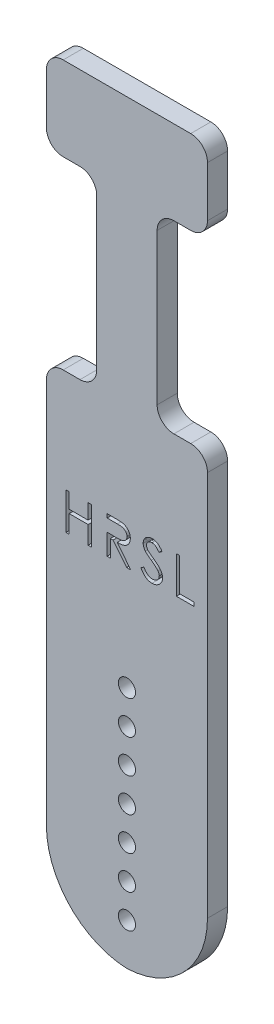
SolidWorks part; units mm, degrees
other "Markup1"
sketch "Sketch7" plane through (-20, 225, -2) normal (-0.1146, 0.1086, -0.9875) x (-0.991, 0.0573, 0.1213)
sketch "Sketch10" plane through (-20, 225, -2) normal (-0.1146, 0.1086, -0.9875) x (-0.991, 0.0573, 0.1213)
sketch "Sketch11" plane through (-20, 225, -2) normal (-0.1146, 0.1086, -0.9875) x (-0.991, 0.0573, 0.1213)
sketch "Sketch13" plane through (-25, 225, -3) normal (-0.1146, 0.1086, -0.9875) x (-0.991, 0.0573, 0.1213)
sketch "Sketch14" plane through (-24, 225, -3) normal (-0.1146, 0.1086, -0.9875) x (-0.991, 0.0573, 0.1213)
sketch "Sketch15" plane through (-24, 225, -3) normal (-0.1146, 0.1086, -0.9875) x (-0.991, 0.0573, 0.1213)
ref_plane "Front Plane" through (0, 0, 0) normal (0, 0, 1) x (1, 0, 0)
ref_plane "Top Plane" through (0, 0, 0) normal (0, 1, 0) x (1, 0, 0)
ref_plane "Right Plane" through (0, 0, 0) normal (1, 0, 0) x (0, 0, -1)
sketch "Sketch1" plane through (0, 0, 0) normal (0, 1, 0) x (1, 0, 0)
  line L1 (-24, 3) -> (24, 3)
  line L2 (-24, 3) -> (-24, -3)
  line L3 (-24, -3) -> (24, -3)
  line L4 (24, 3) -> (24, -3)
  line L5 (-24, 3) -> (24, -3) construction
  line L6 (-24, -3) -> (24, 3) construction
  point P0 (0, 0)
  dimension "D1" = 6
  dimension "D2" = 48
extrude "Boss-Extrude1" add sketch "Sketch1" along normal blind 225
fillet "Fillet1" radius 25 2 edges at (-24, 0, 0) (24, 0, 0)
sketch "Sketch2" plane through (0, 0, 3) normal (0, 0, 1) x (1, 0, 0)
  circle A0 centre (0, 12.5) radius 2.55
extrude "Cut-Extrude1" cut sketch "Sketch2" against normal through all
pattern_linear "LPattern1" count 7 spacing 10 along (0, 1, 0) of "Cut-Extrude1"
sketch "Sketch12" plane through (0, 0, 0) normal (0, 0, 1) x (1, 0, 0)
  line L3 (-24, 200) -> (24, 200)
  line L5 (0, 232.0388) -> (0, 196.5997) construction
  line L6 (-9, 200) -> (-9, 145)
  line L7 (9, 200) -> (9, 145)
  line L8 (9, 145) -> (24, 145)
  line L9 (24, 225) -> (24, 25) construction
  line L10 (24, 145) -> (24, 200)
  line L12 (-9, 145) -> (-24, 145)
  line L13 (-24, 225) -> (-24, 25) construction
  line L14 (-24, 145) -> (-24, 200)
  line L15 (24, 225) -> (-24, 225) construction
  dimension "D1" = 15
  dimension "D2" = 55
  dimension "D3" = 18
  dimension "D4" = 9
  dimension "D5" = 55
  dimension "D6" = 48
  dimension "D7" = 55
  dimension "D8" = 15
  dimension "D9" = 25
extrude "Cut-Extrude2" cut sketch "Sketch12" against normal through all both and the other way through all contours L12 L6 L3 | L3 L7 L8 region at (16.5, 172.5, 0) region at (-16.5, 172.5, 0)
fillet "Fillet2" radius 5 10 edges at (-24, 145, 0) (-9, 145, 0) (24, 145, 0) (9, 145, 0) (9, 200, 0) (-9, 200, 0) (-24, 225, 0) (-24, 200, 0) (24, 200, 0) (24, 225, 0)
sketch "Sketch19" plane through (0, 0, -3) normal (0, 0, -1) x (-1, 0, 0)
  line L0 (18.2062, 114.4599) -> (17.2191, 114.4599)
  line L1 (17.2191, 114.4599) -> (17.2191, 109.9471)
  line L2 (17.2191, 109.9471) -> (11.578, 109.9471)
  line L3 (11.578, 109.9471) -> (11.578, 114.4599)
  line L4 (11.578, 114.4599) -> (10.5909, 114.4599)
  line L5 (10.5909, 114.4599) -> (10.5909, 103.4599)
  line L6 (10.5909, 103.4599) -> (11.578, 103.4599)
  line L7 (11.578, 103.4599) -> (11.578, 108.8189)
  line L8 (11.578, 108.8189) -> (17.2191, 108.8189)
  line L9 (17.2191, 108.8189) -> (17.2191, 103.4599)
  line L10 (17.2191, 103.4599) -> (18.2062, 103.4599)
  line L11 (18.2062, 103.4599) -> (18.2062, 114.4599)
  line L12 (5.9088, 114.4599) -> (3.7075, 114.4599)
  line L13 (2.8988, 108.5368) -> (-1.1425, 103.4599)
  line L14 (-1.1425, 103.4599) -> (0.0783, 103.4599)
  line L15 (0.0783, 103.4599) -> (4.1195, 108.5368)
  line L16 (4.1195, 108.5368) -> (4.9216, 108.5368)
  line L17 (4.9216, 108.5368) -> (4.9216, 103.4599)
  line L18 (4.9216, 103.4599) -> (5.9088, 103.4599)
  line L19 (5.9088, 103.4599) -> (5.9088, 109.665)
  line L21 (4.9216, 109.665) -> (2.9076, 109.6496)
  line L22 (2.8591, 113.3317) -> (4.9216, 113.3317)
  line L23 (-4.1322, 105.5819) -> (-5.0621, 106.1394)
  line L24 (-10.4784, 112.88) -> (-9.5859, 112.2035)
  line L25 (-14.7373, 114.4599) -> (-15.7245, 114.4599)
  line L26 (-15.7245, 114.4599) -> (-15.7245, 104.5881)
  line L27 (-15.7245, 104.5881) -> (-19.9553, 104.5881)
  line L28 (-19.9553, 104.5881) -> (-19.9553, 103.4599)
  line L29 (-19.9553, 103.4599) -> (-14.7373, 103.4599)
  line L30 (-14.7373, 103.4599) -> (-14.7373, 114.4599)
  line L31 (4.9216, 113.3317) -> (5.9088, 113.3317)
  line L32 (4.9216, 109.665) -> (5.9088, 109.665)
  line L33 (5.9088, 113.3317) -> (5.9088, 114.4599)
  spline S0 degree 3 poles (3.7075, 114.4599) (3.4255, 114.4583) (3.0212, 114.4592) (2.5073, 114.4382) (2.1772, 114.4253) (1.8843, 114.4017) (1.5663, 114.3741) (1.3476, 114.3396) (1.2153, 114.31) knots 0 0 0 0 0.338434 0.484822 0.617158 0.734698 0.837385 1 1 1 1
  spline S1 degree 3 poles (1.2153, 114.31) (1.0551, 114.2748) (0.8221, 114.2014) (0.5279, 114.0714) (0.3211, 113.9584) (0.127, 113.8277) (-0.0562, 113.6817) (-0.2296, 113.5211) (-0.3861, 113.3418) (-0.5336, 113.1538) (-0.658, 112.9504) (-0.7653, 112.7377) (-0.8507, 112.5136) (-0.9194, 112.2802) (-0.9854, 111.9488) (-1.0019, 111.692) (-1.0014, 111.5182) knots 0 0 0 0 0.127064 0.188745 0.249132 0.309453 0.369827 0.43065 0.492352 0.554072 0.61569 0.676798 0.738439 0.801317 0.865185 1 1 1 1
  spline S2 degree 3 poles (-1.0014, 111.5182) (-1.0025, 111.2327) (-0.9538, 110.809) (-0.7661, 110.2834) (-0.5767, 109.9246) (-0.3352, 109.6012) (-0.0451, 109.3171) (0.294, 109.0794) (0.6096, 108.9145) (0.8884, 108.8089) (1.118, 108.7346) (1.3684, 108.6773) (1.6372, 108.6258) (1.9256, 108.587) (2.3477, 108.5478) (2.6746, 108.5376) (2.8988, 108.5368) knots 0 0 0 0 0.153721 0.226714 0.299191 0.37119 0.443006 0.516689 0.593217 0.633873 0.676989 0.7229 0.771959 0.824211 0.879379 1 1 1 1
  spline S3 degree 3 poles (2.9076, 109.6496) (2.7253, 109.6467) (2.4615, 109.6563) (2.1221, 109.6763) (1.8957, 109.6981) (1.6883, 109.7263) (1.5, 109.7615) (1.3305, 109.8025) (1.1328, 109.866) (0.9121, 109.9666) (0.6722, 110.1129) (0.4679, 110.297) (0.2952, 110.5075) (0.1567, 110.7389) (0.0249, 111.0731) (-0.0149, 111.3407) (-0.0143, 111.5204) knots 0 0 0 0 0.138913 0.201185 0.259124 0.312255 0.360682 0.405086 0.445102 0.518778 0.589462 0.658462 0.727283 0.796322 0.863175 1 1 1 1
  spline S4 degree 3 poles (-0.0143, 111.5204) (-0.0137, 111.6952) (0.0227, 111.9591) (0.1616, 112.283) (0.3008, 112.5098) (0.4705, 112.7157) (0.6695, 112.8918) (0.8923, 113.0372) (1.1006, 113.13) (1.2868, 113.187) (1.4484, 113.2271) (1.6311, 113.2593) (1.8356, 113.2851) (2.0611, 113.3072) (2.4049, 113.328) (2.6733, 113.3323) (2.8591, 113.3317) knots 0 0 0 0 0.136365 0.204019 0.273064 0.342913 0.410965 0.479169 0.549308 0.587652 0.630647 0.678879 0.731934 0.791111 0.855283 1 1 1 1
  spline S5 degree 3 poles (-5.0621, 106.1394) (-5.2231, 105.8598) (-5.4774, 105.4678) (-5.8772, 105.0239) (-6.1757, 104.7633) (-6.4845, 104.5585) (-6.9088, 104.3654) (-7.2509, 104.3054) (-7.4772, 104.306) knots 0 0 0 0 0.304646 0.438547 0.562322 0.677433 0.786897 1 1 1 1
  spline S6 degree 3 poles (-7.4772, 104.306) (-7.6685, 104.3043) (-7.9535, 104.3379) (-8.3197, 104.4439) (-8.5793, 104.5564) (-8.8216, 104.6926) (-9.0341, 104.8571) (-9.2178, 105.0413) (-9.368, 105.2468) (-9.4832, 105.4678) (-9.6016, 105.7697) (-9.6293, 106.0117) (-9.6322, 106.1702) knots 0 0 0 0 0.18093 0.270088 0.360156 0.448343 0.532666 0.613834 0.693982 0.772716 0.849335 1 1 1 1
  spline S7 degree 3 poles (-9.6322, 106.1702) (-9.6333, 106.3566) (-9.5582, 106.7455) (-9.3577, 107.086) (-9.2378, 107.2499) knots 0 0 0 0 0.477158 1 1 1 1
  spline S8 degree 3 poles (-9.2378, 107.2499) (-9.1364, 107.3837) (-8.9649, 107.5865) (-8.6988, 107.8452) (-8.4666, 108.0622) (-8.2021, 108.2831) (-7.8034, 108.6086) (-7.4786, 108.8425) (-7.2546, 109.004) knots 0 0 0 0 0.18953 0.299198 0.418926 0.548376 0.688136 1 1 1 1
  spline S9 degree 3 poles (-7.2546, 109.004) (-7.032, 109.1597) (-6.7205, 109.3909) (-6.3315, 109.6918) (-6.0887, 109.8875) (-5.8801, 110.0654) (-5.6632, 110.2595) (-5.528, 110.4063) (-5.4521, 110.5001) knots 0 0 0 0 0.347082 0.495568 0.628357 0.74552 0.845831 1 1 1 1
  spline S10 degree 3 poles (-5.4521, 110.5001) (-5.3549, 110.6261) (-5.2193, 110.8194) (-5.0744, 111.095) (-4.9902, 111.304) (-4.9195, 111.5153) (-4.8554, 111.8043) (-4.8365, 112.0264) (-4.8373, 112.1748) knots 0 0 0 0 0.262559 0.388264 0.512667 0.633722 0.755394 1 1 1 1
  spline S11 degree 3 poles (-4.8373, 112.1748) (-4.8368, 112.405) (-4.8802, 112.7474) (-5.0267, 113.179) (-5.1783, 113.4818) (-5.374, 113.7582) (-5.6004, 114.0116) (-5.8701, 114.2246) (-6.166, 114.4107) (-6.4899, 114.5562) (-6.9458, 114.7044) (-7.3075, 114.7388) (-7.5477, 114.7419) knots 0 0 0 0 0.16578 0.24628 0.327461 0.408797 0.489715 0.571376 0.655523 0.741019 0.826547 1 1 1 1
  spline S12 degree 3 poles (-7.5477, 114.7419) (-7.8051, 114.7423) (-8.1917, 114.695) (-8.6794, 114.5232) (-8.973, 114.3782) (-9.2029, 114.2332) (-9.3782, 114.1011) (-9.5558, 113.9491) (-9.7372, 113.7767) (-9.9193, 113.5823) (-10.1742, 113.2871) (-10.3586, 113.0487) (-10.4784, 112.88) knots 0 0 0 0 0.213252 0.31883 0.426794 0.483646 0.543604 0.608308 0.677127 0.750686 0.828713 1 1 1 1
  spline S13 degree 3 poles (-9.5859, 112.2035) (-9.4837, 112.3384) (-9.3285, 112.5275) (-9.1222, 112.7648) (-8.9759, 112.9134) (-8.8396, 113.0476) (-8.7072, 113.1625) (-8.5807, 113.2592) (-8.4213, 113.3624) (-8.2211, 113.4647) (-7.8838, 113.5814) (-7.6162, 113.6126) (-7.4375, 113.6137) knots 0 0 0 0 0.189629 0.274184 0.352183 0.423199 0.488551 0.548473 0.60144 0.701198 0.799592 1 1 1 1
  spline S14 degree 3 poles (-7.4375, 113.6137) (-7.2189, 113.6169) (-6.8976, 113.5701) (-6.5136, 113.3959) (-6.273, 113.2191) (-6.0729, 113.0094) (-5.8779, 112.6864) (-5.8249, 112.4063) (-5.8245, 112.2211) knots 0 0 0 0 0.275903 0.402371 0.528414 0.650356 0.765895 1 1 1 1
  spline S15 degree 3 poles (-5.8245, 112.2211) (-5.8208, 112.1027) (-5.8476, 111.9269) (-5.9071, 111.6961) (-5.9772, 111.5235) (-6.0742, 111.3491) (-6.2542, 111.0955) (-6.4257, 110.9191) (-6.5495, 110.7998) knots 0 0 0 0 0.214746 0.322939 0.434116 0.553412 0.686073 1 1 1 1
  spline S16 degree 3 poles (-6.5495, 110.7998) (-6.606, 110.748) (-6.7094, 110.6629) (-6.8735, 110.5406) (-7.0415, 110.413) (-7.2425, 110.2651) (-7.5757, 110.028) (-7.8398, 109.8371) (-8.0281, 109.7047) knots 0 0 0 0 0.124952 0.218094 0.333502 0.468789 0.624938 1 1 1 1
  spline S17 degree 3 poles (-8.0281, 109.7047) (-8.2595, 109.537) (-8.5938, 109.2911) (-9.0058, 108.9497) (-9.2744, 108.7096) (-9.516, 108.4785) (-9.7279, 108.2536) (-9.9124, 108.0365) (-10.111, 107.7581) (-10.3135, 107.4162) (-10.543, 106.8685) (-10.6192, 106.4379) (-10.6194, 106.1548) knots 0 0 0 0 0.187773 0.272396 0.351321 0.424335 0.491909 0.554233 0.611268 0.716348 0.81454 1 1 1 1
  spline S18 degree 3 poles (-10.6194, 106.1548) (-10.6224, 105.9593) (-10.5905, 105.6698) (-10.4972, 105.2955) (-10.3935, 105.0286) (-10.2668, 104.7686) (-10.106, 104.5222) (-9.9196, 104.2839) (-9.7057, 104.0602) (-9.4718, 103.8548) (-9.2245, 103.6721) (-8.9635, 103.5198) (-8.6901, 103.3955) (-8.4045, 103.2984) (-8.0019, 103.2027) (-7.6882, 103.177) (-7.4772, 103.1778) knots 0 0 0 0 0.121775 0.18092 0.240256 0.300114 0.361146 0.423501 0.488669 0.553954 0.617581 0.680238 0.742187 0.804663 0.868259 1 1 1 1
  spline S19 degree 3 poles (-7.4772, 103.1778) (-7.3119, 103.1768) (-7.0667, 103.1968) (-6.7454, 103.2509) (-6.5141, 103.3142) (-6.2877, 103.3911) (-6.0672, 103.4858) (-5.8526, 103.5994) (-5.6426, 103.7291) (-5.4378, 103.8802) (-5.24, 104.0561) (-5.0429, 104.252) (-4.8521, 104.4733) (-4.664, 104.7164) (-4.4145, 105.0824) (-4.2428, 105.377) (-4.1322, 105.5819) knots 0 0 0 0 0.113696 0.169178 0.224159 0.27872 0.333794 0.389241 0.445822 0.503704 0.564294 0.627975 0.695038 0.765373 0.839611 1 1 1 1
extrude "Cut-Extrude5" cut sketch "Sketch19" against normal through all both
